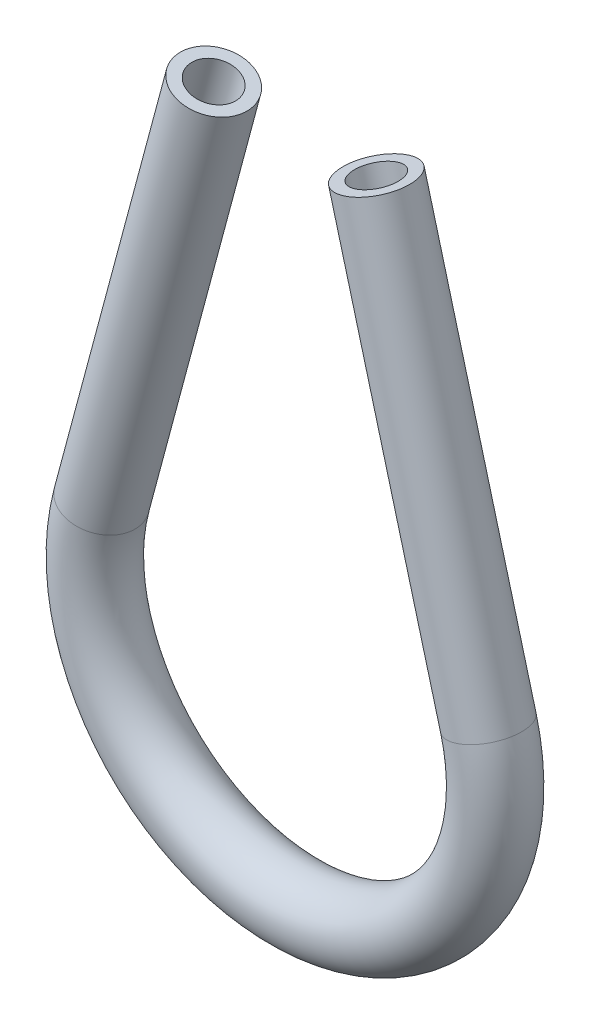
SolidWorks part; units mm, degrees
material "PTFE (general)"
ref_plane "Front Plane" through (0, 0, 0) normal (0, 0, 1) x (1, 0, 0)
ref_plane "Top Plane" through (0, 0, 0) normal (0, 1, 0) x (1, 0, 0)
ref_plane "Right Plane" through (0, 0, 0) normal (1, 0, 0) x (0, 0, -1)
sketch "Sketch1" plane through (0, 0, 0) normal (0, 0, 1) x (1, 0, 0)
  line L0 (-138.9852, -15.4299) -> (-159.619, -92.4363) construction
  line L1 (-109.0238, -15.4299) -> (-88.39, -92.4363) construction
  line L2 (-138.9852, -15.4299) -> (-159.619, -92.4363)
  line L3 (-109.0238, -15.4299) -> (-88.39, -92.4363)
  arc A0 (-159.619, -92.4363) -> (-88.39, -92.4363) centre (-124.0045, -101.9792) ccw construction
  arc A1 (-159.619, -92.4363) -> (-88.39, -92.4363) centre (-124.0045, -101.9792) ccw
sketch "Sketch2" plane through (-3.4457, 12.8596, 0) normal (0.2588, -0.9659, 0) x (0.9659, 0.2588, 0)
  circle A0 centre (-109.3024, 0) radius 4.1672
  circle A1 centre (-109.3024, 0) radius 6.35
  dimension "D1" = 8.3344
  dimension "D2" = 12.7
sweep "Sweep1" add profiles "Sketch2" path "Sketch1"
